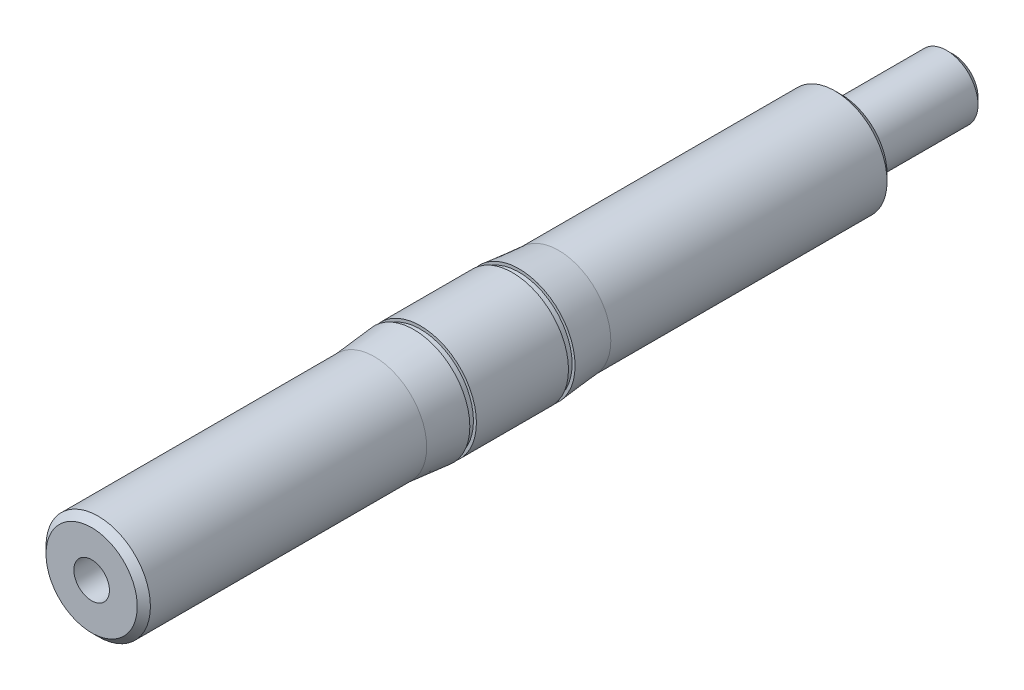
SolidWorks part; units mm, degrees
material "AISI 4340 Steel, normalized"
ref_plane "Front Plane" through (0, 0, 0) normal (0, 0, 1) x (1, 0, 0)
ref_plane "Top Plane" through (0, 0, 0) normal (0, 1, 0) x (1, 0, 0)
ref_plane "Right Plane" through (0, 0, 0) normal (1, 0, 0) x (0, 0, -1)
sketch "Sketch1" plane through (0, 0, 0) normal (1, 0, 0) x (0, 0, -1)
  line L0 (-83.8048, 0) -> (83.8048, 0) construction
  line L1 (-8, 8.5) -> (-14, 7.9375)
  line L2 (-57, 0) -> (57, 0)
  line L3 (35, 15.4987) -> (35, -15.4987) construction
  line L4 (-7, 8.5) -> (-7, 8.05)
  line L5 (8, 8.05) -> (8, 8.5)
  line L6 (7, 8.05) -> (8, 8.05)
  line L7 (-7, 8.5) -> (7, 8.5)
  line L8 (7, 8.5) -> (7, 8.05)
  line L9 (-35, 15.4987) -> (-35, -15.4987) construction
  line L10 (-7, 8.05) -> (-8, 8.05)
  line L11 (-8, 8.05) -> (-8, 8.5)
  line L12 (-14, 7.9375) -> (-35, 7.9375)
  line L13 (0, 0) -> (0, 15.0999) construction
  line L14 (-57, 7.9375) -> (-35, 7.9375)
  line L15 (-57, 7.9375) -> (-57, 0)
  line L17 (57, 7.9375) -> (57, 0)
  line L18 (57, 7.9375) -> (35, 7.9375)
  line L19 (14, 7.9375) -> (35, 7.9375)
  line L20 (8, 8.5) -> (14, 7.9375)
  point P12 (-35, 0)
  point P17 (0, 8.5)
  point P28 (0, 8.5)
  dimension "D1" = 22
  dimension "D2" = 17
  dimension "D3" = 6
  dimension "D4" = 14
  dimension "D5" = 16.1
  dimension "D6" = 1
  dimension "D7" = 15.875
  dimension "D8" = 35
revolve "Revolve1" add sketch "Sketch1" angle 360 about L0
cosmetic thread "Cosmetic Thread1"
cosmetic thread "Cosmetic Thread2"
chamfer "Chamfer1" distance 1 angle 45 2 edges at (7.9375, 0, 57) (7.9375, 0, -57)
sketch "Sketch2" [suppressed] plane through (0, 0, 0) normal (1, 0, 0) x (0, 0, -1)
  line L0 (64.5155, 0) -> (-64.5155, 0) construction
  line L1 (0, 0) -> (0, 23.4714) construction
  line L2 (-43, -15.7295) -> (-25, -15.7295)
  line L3 (-43, -15.7295) -> (-43, 15.7295)
  line L4 (-43, 15.7295) -> (-25, 15.7295)
  line L5 (-25, -15.7295) -> (-25, 15.7295)
  line L6 (-43, -15.7295) -> (-25, 15.7295) construction
  line L7 (-43, 15.7295) -> (-25, -15.7295) construction
  line L8 (43, 15.7295) -> (25, -15.7295) construction
  line L9 (43, -15.7295) -> (25, 15.7295) construction
  line L10 (25, -15.7295) -> (25, 15.7295)
  line L11 (43, 15.7295) -> (25, 15.7295)
  line L12 (43, -15.7295) -> (43, 15.7295)
  line L13 (43, -15.7295) -> (25, -15.7295)
  point P3 (-34, 0)
  point P14 (34, 0)
  dimension "D1" = 34
  dimension "D2" = 18
split line "Split Line1" [suppressed]
sketch "Sketch3" plane through (0, 0, -57) normal (0, 0, 1) x (1, 0, 0)
  circle A0 centre (0, 0) radius 4.7625
  dimension "D1" = 9.525
extrude "Boss-Extrude1" add sketch "Sketch3" against normal blind 17
cosmetic thread "Cosmetic Thread3"
chamfer "Chamfer2" distance 1 angle 45 1 edges at (4.7625, 0, -74)
hole_wizard "1/4-28 Tapped Hole1" positions "Sketch7" profile "Sketch6" tap size "1/4-28" standard "ANSI Inch"
sketch "Sketch7" plane through (0, 0, 57) normal (0, 0, 1) x (1, 0, 0)
  point P0 (0, 0)
sketch "Sketch6" plane through (0, 0, 57) normal (1, 0, 0) x (0, -1, 0)
  line L0 (0, 0) -> (0, 17.0454)
  line L1 (0, 17.0454) -> (2.7051, 15.42)
  line L2 (2.7051, 15.42) -> (2.7051, 0)
  line L5 (2.7051, 0) -> (0, 0)
  line L10 (0, 17.0454) -> (-2.7051, 15.42) construction
  line L11 (0, -6.35) -> (0, 107.95) construction
  dimension "Tap Drill Dia." = 5.4102
  dimension "Tap Drill Depth" = 15.42
  dimension "Drill Angle" = 118
cosmetic thread "Hole Thread1" parameters "D1"=12.7, "D2"=6.35
sketch "Sketch4" [suppressed] plane through (0, 0, 0) normal (0, 0, 1) x (1, 0, 0)
  circle A0 centre (0, 0) radius 7.9375
  circle A1 centre (0, 0) radius 7.9375 construction
  circle A2 centre (0, 0) radius 17.1306
extrude "Boss-Extrude2" [suppressed] add sketch "Sketch4" along normal blind 9 and the other way blind 9 separate body
